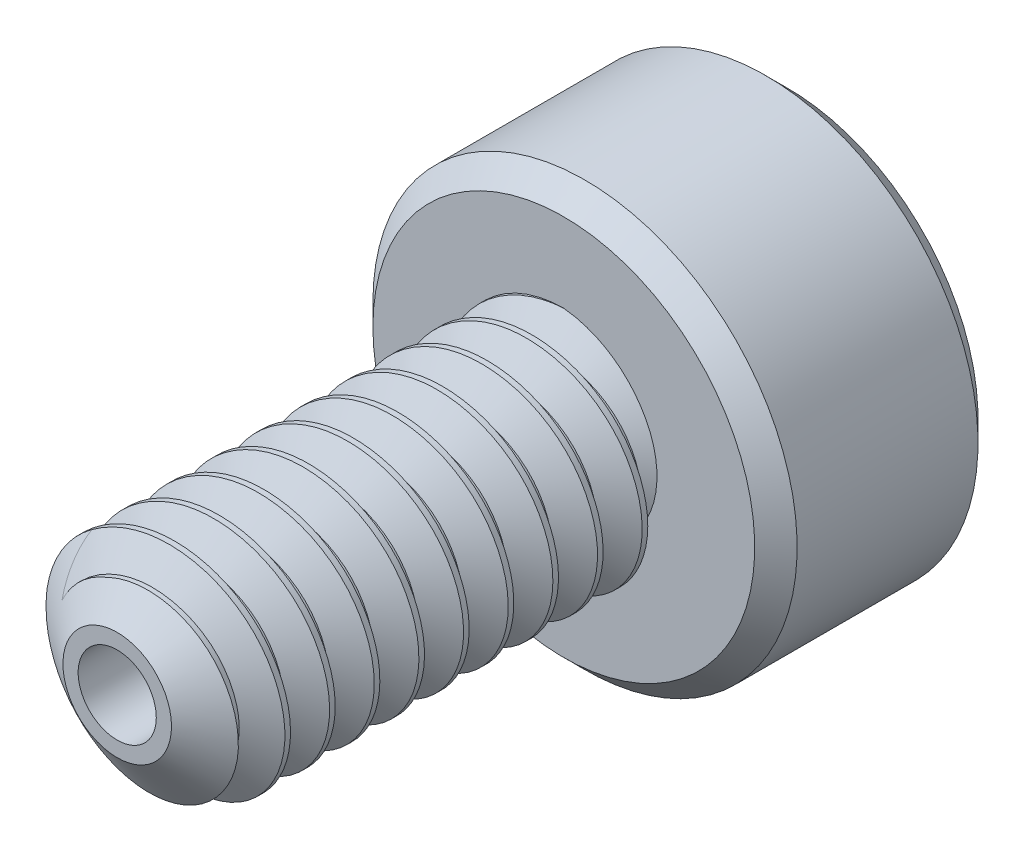
SolidWorks part; units mm, degrees
other "DetailItem1"
ref_plane "Front Plane" through (0, 0, 0) normal (0, 0, 1) x (1, 0, 0)
ref_plane "Top Plane" through (0, 0, 0) normal (0, 1, 0) x (1, 0, 0)
ref_plane "Right Plane" through (0, 0, 0) normal (1, 0, 0) x (0, 0, -1)
sketch "Sketch1" plane through (0, 0, 0) normal (0, 0, 1) x (1, 0, 0)
  circle A0 centre (0, 0) radius 1
  dimension "OD" = 2
extrude "Extrude1" add sketch "Sketch1" against normal blind 4
sketch "Sketch2" plane through (0, 0, 0) normal (0, 0, 1) x (1, 0, 0)
  circle A0 centre (0, 0) radius 1 construction
  circle A1 centre (0, 0) radius 1
curve "Helix/Spiral1" pitch 0.4 height 4.4 radius 1 centre (0, 0, 0) axis (0, 0, -1) start towards (0, 1, 0) parameters "pitch"=0.4
sketch "Sketch3" plane through (0, 0, 0) normal (1, 0, 0) x (0, 0, -1)
  line L0 (-0.35, 1) -> (-0.2, 0.7402)
  line L1 (-0.2, 0.7402) -> (-0.15, 0.7402)
  line L2 (-0.15, 0.7402) -> (0, 1)
  line L3 (-0.35, 1) -> (0, 1)
  line L4 (-0.175, 1) -> (-0.175, 0.7402) construction
  line L5 (-0.275, 0.8701) -> (-0.075, 0.8701) construction
  line L6 (0, 1) -> (0, -1) construction
  dimension "D1" = 0.05
  dimension "D2" = 0.2
  dimension "D3" = 60
sweep "Cut-Sweep1" cut profiles "Sketch3" path "Helix/Spiral1" align with end faces yes
sketch "Sketch4" plane through (0, 0, 0) normal (1, 0, 0) x (0, 0, -1)
  line L0 (0.3598, 1) -> (0, 0.4862)
  line L1 (0, 0.4862) -> (0, 1)
  line L2 (0.3598, 1) -> (0, 1)
  line L3 (-0.35, 1) -> (0, 1) construction
  line L4 (0, 0) -> (7.0209, 0) construction
  dimension "D1" = 55
  dimension "D2" = 0.254
revolve "Cut-Revolve1" cut sketch "Sketch4" angle 360 about L4
sketch "Sketch6" plane through (0, 0, -4) normal (0, 0, -1) x (-1, 0, 0)
  circle A0 centre (0, 0) radius 1.9
  dimension "head dia" = 3.8
extrude "Extrude2" add sketch "Sketch6" along normal blind 2
sketch "Sketch7" plane through (0, 0, -6) normal (0, 0, -1) x (-1, 0, 0)
  line L1 (0, 0.866) -> (-0.75, 0.433)
  line L2 (-0.75, 0.433) -> (-0.75, -0.433)
  line L3 (-0.75, -0.433) -> (0, -0.866)
  line L4 (0, -0.866) -> (0.75, -0.433)
  line L5 (0.75, -0.433) -> (0.75, 0.433)
  line L6 (0.75, 0.433) -> (0, 0.866)
  circle A0 centre (0, 0) radius 0.75 construction
  dimension "hex dia" = 1.5
extrude "Cut-Extrude1" cut sketch "Sketch7" against normal blind 1.125
sketch "Sketch8" plane through (0, 0, -6) normal (0, 0, -1) x (-1, 0, 0)
  circle A0 centre (0, 0) radius 0.866
extrude "Cut-Extrude2" cut sketch "Sketch8" against normal through all draft 45
chamfer "Chamfer1" distance 0.19 angle 45 2 edges at (-1.9, 0, -6) (-1.9, 0, -4)
sketch "Sketch10" plane through (0, 0, -4) normal (0, 0, 1) x (1, 0, 0)
  circle A1 centre (0, 0) radius 1
  circle A2 centre (0, 0) radius 1
  dimension "D1" = 0
ref_plane "Plane1" through (0, 0, 0) normal (0, 0, 1) x (1, 0, 0)
extrude "partial thread" [suppressed] add sketch "Sketch10" along normal up to surface (12.7 mm away) separate body up to plane "Plane1"
chamfer "Chamfer2" [suppressed] distance 0.04 angle 45
combine bodies "Combine1" [suppressed] operation type add bodies to combine 107 108
sketch "Sketch9" plane through (0, 0, 0) normal (1, 0, 0) x (0, 0, -1)
  line L0 (0, 1) -> (0, -1) construction
  line L1 (1, 1) -> (1, -1) construction
  dimension "D1" = 1
sketch "Sketch11" plane through (0, 0, 0) normal (0, 0, 1) x (1, 0, 0)
  circle A0 centre (0, 0) radius 0.35
  dimension "Vent Dia" = 0.7
extrude "Cut-Extrude3" cut sketch "Sketch11" against normal through all
equation "\"D3@Helix/Spiral1\" = \"screw length@Extrude1\"+\"pitch@Helix/Spiral1\""
equation "\"D1@Sketch3\" = \"pitch@Helix/Spiral1\"*.125"
equation "\"D2@Sketch3\" = \"pitch@Helix/Spiral1\"*.5"
equation "\"D1@Cut-Extrude1\" = \"hex dia@Sketch7\"*.75"
equation "\"D1@Chamfer1\" = \"head dia@Sketch6\"*.05"
equation "\"D1@Sketch9\" = \"pitch@Helix/Spiral1\"*2.5"
equation "\"D1@Chamfer2\"=\"OD@Sketch1\"*.02"
